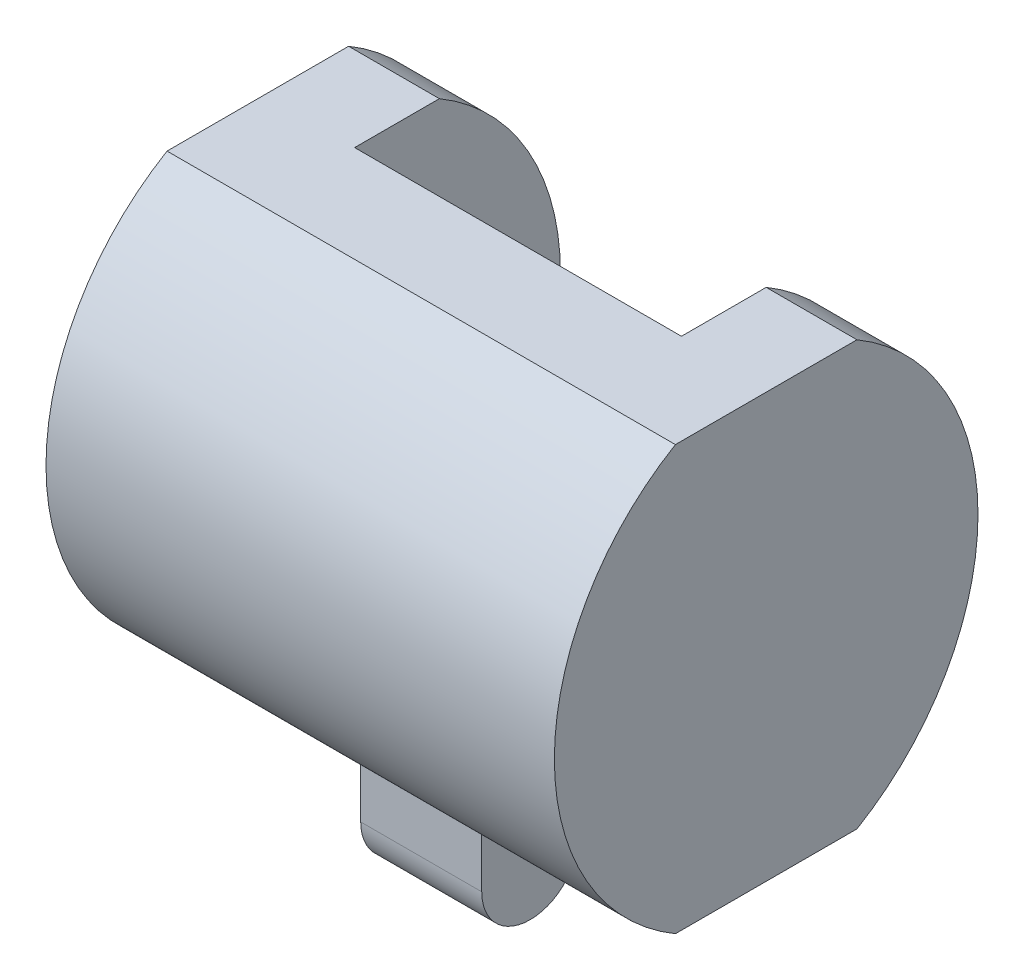
SolidWorks part; units mm, degrees
ref_plane "Front Plane" through (0, 0, 0) normal (0, 0, 1) x (1, 0, 0)
ref_plane "Top Plane" through (0, 0, 0) normal (0, 1, 0) x (1, 0, 0)
ref_plane "Right Plane" through (0, 0, 0) normal (1, 0, 0) x (0, 0, -1)
sketch "Sketch1" plane through (0, 0, 0) normal (1, 0, 0) x (0, 0, -1)
  line L0 (0, 17.5) -> (0, -17.5) construction
  line L1 (0, 17.5) -> (-15, 17.5)
  line L2 (10, 17.5) -> (10, -17.5) construction
  line L3 (0, -17.5) -> (-15, -17.5)
  line L4 (-15, 17.5) -> (-15, -17.5) construction
  line L5 (0, 0) -> (10, 0) construction
  line L6 (0, 0) -> (-8.6603, 5) construction
  line L7 (0, 0) -> (-8.6603, 5) construction
  line L8 (-15, 0) -> (-25, 0) construction
  arc A0 (0, -17.5) -> (0, 17.5) centre (-10.3125, 0) ccw
  arc A1 (-15, 17.5) -> (-15, -17.5) centre (-4.6875, 0) ccw
  dimension "D3" = 25
  dimension "D1" = 35
extrude "Boss-Extrude1" add sketch "Sketch1" against normal mid plane 42
sketch "Sketch2" plane through (0, 0, 0) normal (1, 0, 0) x (0, 0, -1)
  line L0 (0, 17.5) -> (-15, 17.5) construction
  line L1 (-15, -17.5) -> (0, -17.5) construction
  line L2 (-17, 0) -> (-25, 0) construction
  line L4 (-15, -17.5) -> (0, -17.5)
  line L5 (0, 17.5) -> (-15, 17.5)
  line L6 (-7, -17.5) -> (0, -17.5)
  line L7 (0, 17.5) -> (-7, 17.5)
  arc A0 (-7, 17.5) -> (-7, -17.5) centre (3.3125, 0) ccw
  arc A1 (-15, 17.5) -> (-15, -17.5) centre (-4.6875, 0) ccw construction
  arc A4 (-15, 17.5) -> (-15, -17.5) centre (-4.6875, 0) ccw
  arc A5 (0, -17.5) -> (0, 17.5) centre (-10.3125, 0) ccw
  arc A7 (0, -17.5) -> (0, 17.5) centre (-10.3125, 0) ccw
  dimension "D1" = 0
  dimension "D2" = 8
extrude "Cut-Extrude1" cut sketch "Sketch2" against normal mid plane 27
sketch "Sketch3" plane through (0, 0, 0) normal (1, 0, 0) x (0, 0, -1)
  line L0 (-15, -17.5) -> (-15, -22.5)
  line L1 (-15, -17.5) -> (0, -17.5) construction
  line L2 (-7, -22.5) -> (-7, -17.5)
  line L3 (-7, -17.5) -> (-15, -17.5)
  line L4 (-11, -26.5) -> (-11, -17.5) construction
  arc A0 (-15, -22.5) -> (-7, -22.5) centre (-11, -22.5) ccw
  point P9 (-15, -16)
  point P11 (0, 0)
  dimension "D1" = 8
  dimension "D2" = 9
extrude "Boss-Extrude2" add sketch "Sketch3" along normal mid plane 10
